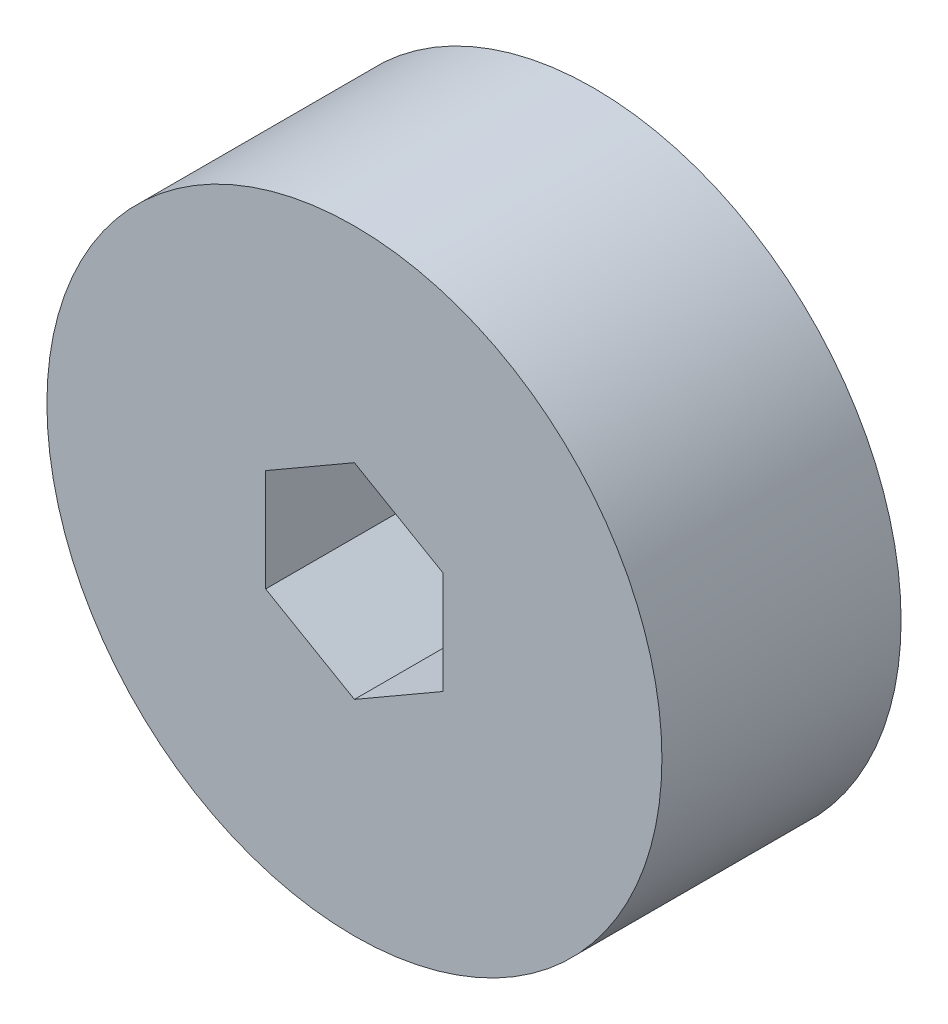
SolidWorks part; units mm, degrees
ref_plane "Front Plane" through (0, 0, 0) normal (0, 0, 1) x (1, 0, 0)
ref_plane "Top Plane" through (0, 0, 0) normal (0, 1, 0) x (1, 0, 0)
ref_plane "Right Plane" through (0, 0, 0) normal (1, 0, 0) x (0, 0, -1)
sketch "Sketch1" plane through (0, 0, 0) normal (0, 0, 1) x (1, 0, 0)
  line L0 (0, -3) -> (0, 3) construction
  line L1 (-2.5981, -1.5) -> (2.5981, 1.5) construction
  line L2 (-2.5981, 1.5) -> (2.5981, -1.5) construction
  line L3 (0, 3) -> (2.5981, 1.5)
  line L4 (2.5981, 1.5) -> (2.5981, -1.5)
  line L5 (2.5981, -1.5) -> (0, -3)
  line L6 (0, -3) -> (-2.5981, -1.5)
  line L7 (-2.5981, -1.5) -> (-2.5981, 1.5)
  line L8 (-2.5981, 1.5) -> (0, 3)
  circle A0 centre (0, 0) radius 9
  circle A2 centre (0, 0) radius 3 construction
  point P7 (0, 0)
  point P9 (0, 0)
  point P13 (0, 0)
  point P14 (0, 0)
extrude "Boss-Extrude1" add sketch "Sketch1" along normal blind 7
ref_plane "Plane1" [suppressed] through (0, 0, 0) normal (-1, 0, 0) x (0, 0, 1)
sketch "Sketch5" [suppressed] plane through (0, 0, 0) normal (-1, 0, 0) x (0, 0, 1)
  line L0 (7, 5) -> (7, -5) construction
  line L1 (7, 0) -> (3.5, 0) construction
  circle A0 centre (3.5, 0) radius 1.55
extrude "Cut-Extrude1" [suppressed] cut sketch "Sketch5" against normal blind 5 and the other way blind 5
ref_plane "Plane2" [suppressed] through (-3.5, 0, 0) normal (-1, 0, 0) x (0, 0, 1)
ref_plane "Plane3" [suppressed] through (3.5, 0, 0) normal (-1, 0, 0) x (0, 0, 1)
sketch "Sketch6" [suppressed] plane through (-3.5, 0, 0) normal (-1, 0, 0) x (0, 0, 1)
  circle A0 centre (3.5, 0) radius 3
extrude "Cut-Extrude2" [suppressed] cut sketch "Sketch6" along normal blind 5.5
sketch "Sketch7" [suppressed] plane through (3.5, 0, 0) normal (-1, 0, 0) x (0, 0, 1)
  circle A0 centre (3.5, 0) radius 3
extrude "Cut-Extrude3" [suppressed] cut sketch "Sketch7" against normal blind 5.5 contours A0
